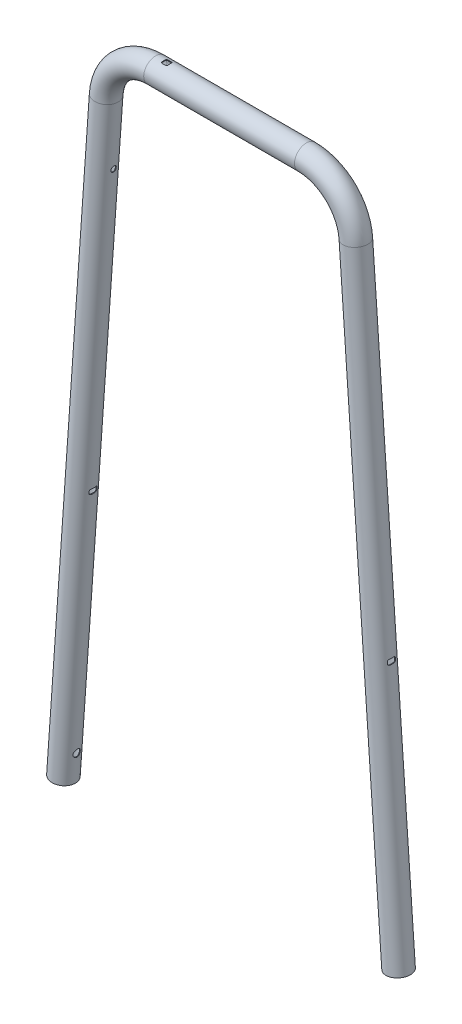
SolidWorks part; units mm, degrees
ref_plane "Front Plane" through (0, 0, 0) normal (0, 0, 1) x (1, 0, 0)
ref_plane "Top Plane" through (0, 0, 0) normal (0, 1, 0) x (1, 0, 0)
ref_plane "Right Plane" through (0, 0, 0) normal (1, 0, 0) x (0, 0, -1)
sketch "Sketch1" plane through (0, 0, 0) normal (0, 0, 1) x (1, 0, 0)
  line L0 (0, 0) -> (0, 595.2821) construction
  line L1 (0, 0) -> (414.971, 0) construction
  line L2 (-83.634, 567.016) -> (83.634, 567.016)
  line L3 (138.5, 515.8526) -> (185.9199, -162.284)
  line L4 (-138.5, 515.8526) -> (-185.9199, -162.284)
  line L5 (-185.9199, -162.284) -> (-455.792, -162.284) construction
  arc A0 (138.5, 515.8526) -> (83.634, 567.016) centre (83.634, 512.016) ccw
  arc A1 (-138.5, 515.8526) -> (-83.634, 567.016) centre (-83.634, 512.016) cw
  point P12 (134.9223, 567.016)
  point P17 (0, 567.016)
  dimension "D4" = 55
  dimension "D1" = 277
  dimension "D2" = 8
  dimension "D3" = 729.3
ref_plane "Plane1" through (-185.9199, -162.284, 0) normal (-0.0698, -0.9976, 0) x (-0.9976, 0.0698, 0)
sketch "Sketch2" plane through (-185.9199, -162.284, 0) normal (-0.0698, -0.9976, 0) x (-0.9976, 0.0698, 0)
  circle A0 centre (0, 0) radius 13.2
  circle A1 centre (0, 0) radius 12.4
  dimension "D1" = 0.8
  dimension "D2" = 26.4
sweep "Sweep2" add profiles "Sketch2" path "Sketch1"
sketch "Sketch6" plane through (-12.1975, -174.4319, 0) normal (-0.0698, -0.9976, 0) x (0.9976, -0.0698, 0)
  line L0 (-174.1467, 0) -> (-186.5467, 0)
  line L1 (-174.1467, 0) -> (-174.1467, 12.4)
  circle A0 centre (-174.1467, 0) radius 12.4 construction
  circle A1 centre (-174.1467, 0) radius 12.4 construction
ref_plane "Plane3" through (-185.9199, -162.284, 0) normal (-0.9976, 0.0698, 0) x (0, 0, 1)
ref_plane "Plane4" through (0, 580.216, 0) normal (0, 1, 0) x (1, 0, 0)
sketch "Sketch17" plane through (-185.9199, -162.284, 0) normal (-0.9976, 0.0698, 0) x (0, 0, 1)
  line L0 (0, 0) -> (0, 30) construction
  line L1 (-13.2, 0) -> (13.2, 0) construction
  line L2 (0, 30) -> (0, 236.8) construction
  circle A0 centre (0, 30) radius 4.05
  dimension "D3" = 8.1
  dimension "D1" = 30
  dimension "D2" = 236.8
extrude "Cut-Extrude6" cut sketch "Sketch17" against normal blind 50
sketch "Sketch18" plane through (-185.9199, -162.284, 0) normal (-0.9976, 0.0698, 0) x (0, 0, 1)
  line L0 (0, 0) -> (0, 292) construction
  line L1 (-12.4, 0) -> (12.4, 0) construction
  line L3 (-2.5, 294.75) -> (2.5, 294.75)
  line L4 (-4.5, 292.75) -> (-4.5, 291.25)
  line L5 (-2.5, 289.25) -> (2.5, 289.25)
  line L6 (4.5, 292.75) -> (4.5, 291.25)
  line L7 (-4.5, 294.75) -> (4.5, 289.25) construction
  line L8 (-4.5, 289.25) -> (4.5, 294.75) construction
  arc A0 (-2.5, 289.25) -> (-4.5, 291.25) centre (-2.5, 291.25) cw
  arc A1 (4.5, 291.25) -> (2.5, 289.25) centre (2.5, 291.25) cw
  arc A2 (2.5, 294.75) -> (4.5, 292.75) centre (2.5, 292.75) cw
  arc A3 (-2.5, 294.75) -> (-4.5, 292.75) centre (-2.5, 292.75) ccw
  dimension "D3" = 2
  dimension "D1" = 5.5
  dimension "D2" = 9
  dimension "D4" = 292
extrude "Cut-Extrude7" cut sketch "Sketch18" against normal blind 50 and the other way blind 50
mirror "Mirror2" about plane through (0, 0, 0) normal (1, 0, 0) of "Cut-Extrude6", "Cut-Extrude7"
sketch "Sketch19" plane through (-185.9199, -162.284, 0) normal (-0.9976, 0.0698, 0) x (0, 0, 1)
  line L0 (0, 0) -> (0, 513) construction
  line L1 (-12.4, 0) -> (12.4, 0) construction
  circle A0 centre (0, 513) radius 4
  dimension "D2" = 8
  dimension "D1" = 513
extrude "Cut-Extrude8" cut sketch "Sketch19" along normal blind 50
sketch "Sketch20" plane through (0, 580.216, 0) normal (0, 1, 0) x (1, 0, 0)
  line L0 (-199.0878, 0) -> (-71.2, 0) construction
  circle A0 centre (-71.2, 0) radius 3.25
  ellipse E0 centre (-185.9199, 0) end of major axis (-185.9199, 13.2) minor radius 13.1678 construction
  ellipse E1 centre (-138.5, 0) end of major axis (-138.5, 13.2) minor radius 13.1678 construction
  dimension "D2" = 6.5
  dimension "D1" = 67.3
extrude "Cut-Extrude9" cut sketch "Sketch20" against normal blind 50
sketch "Sketch21" plane through (0, 580.216, 0) normal (0, 1, 0) x (1, 0, 0)
  line L0 (-199.0878, 0) -> (-71.2, 0) construction
  line L2 (-73.45, -3.25) -> (-68.95, -3.25)
  line L3 (-74.45, -2.25) -> (-74.45, 2.25)
  line L4 (-73.45, 3.25) -> (-68.95, 3.25)
  line L5 (-67.95, -2.25) -> (-67.95, 2.25)
  line L6 (-74.45, -3.25) -> (-67.95, 3.25) construction
  line L7 (-74.45, 3.25) -> (-67.95, -3.25) construction
  arc A0 (-73.45, 3.25) -> (-74.45, 2.25) centre (-73.45, 2.25) ccw
  arc A1 (-74.45, -2.25) -> (-73.45, -3.25) centre (-73.45, -2.25) ccw
  arc A2 (-68.95, 3.25) -> (-67.95, 2.25) centre (-68.95, 2.25) cw
  arc A3 (-67.95, -2.25) -> (-68.95, -3.25) centre (-68.95, -2.25) cw
  ellipse E0 centre (-185.9199, 0) end of major axis (-185.9199, 13.2) minor radius 13.1678 construction
  dimension "D3" = 1
  dimension "D4" = 1
  dimension "D1" = 6.5
  dimension "D2" = 6.5
extrude "Cut-Extrude10" cut sketch "Sketch21" against normal blind 10
sketch "Sketch22" plane through (-185.9199, -162.284, 0) normal (-0.9976, 0.0698, 0) x (0, 0, 1)
  line L0 (-12.4, 0) -> (12.4, 0) construction
  circle A0 centre (0, 613) radius 3.05
  dimension "D1" = 613
extrude "Cut-Extrude11" cut sketch "Sketch22" against normal up to next and the other way up to next
